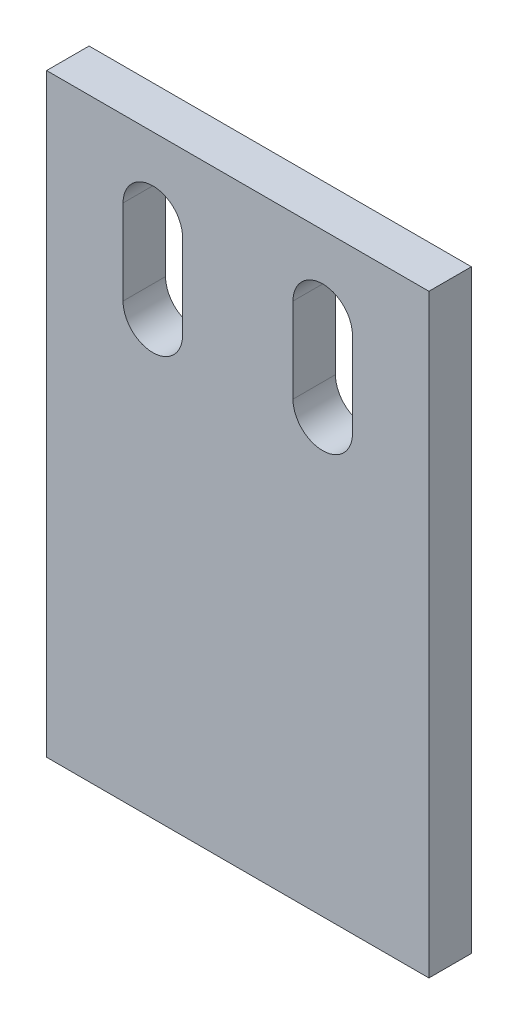
SolidWorks part; units mm, degrees
note: The reader was unsure of these and kept them because the rebuilt part matched: thickness of "Базовая кромка1", "Листовой металл1".
material "Простая углеродистая сталь"
ref_plane "Спереди" through (0, 0, 0) normal (0, 0, 1) x (1, 0, 0)
ref_plane "Сверху" through (0, 0, 0) normal (0, 1, 0) x (1, 0, 0)
ref_plane "Справа" through (0, 0, 0) normal (1, 0, 0) x (0, 0, -1)
sketch "Эскиз1" plane through (0, 0, 0) normal (0, 0, 1) x (1, 0, 0)
  line L0 (0, 0) -> (90, 0)
  line L1 (90, 0) -> (90, -140)
  line L5 (0, -140) -> (0, 0)
  line L6 (0, -140) -> (90, -140)
  line L7 (45, 0) -> (45, -41.8938) construction
  line L8 (25, -18) -> (25, -38) construction
  line L9 (32, -18) -> (32, -38)
  line L10 (18, -18) -> (18, -38)
  line L11 (65, -18) -> (65, -38) construction
  line L12 (58, -18) -> (58, -38)
  line L13 (72, -18) -> (72, -38)
  arc A0 (32, -18) -> (18, -18) centre (25, -18) ccw
  arc A1 (18, -38) -> (32, -38) centre (25, -38) ccw
  arc A2 (58, -18) -> (72, -18) centre (65, -18) cw
  arc A3 (72, -38) -> (58, -38) centre (65, -38) cw
  point P9 (25, -28)
  point P16 (65, -28)
  dimension "D3" = 20
  dimension "D1" = 14
  dimension "D2" = 90
  dimension "D4" = 140
  dimension "D5" = 28
  dimension "D6" = 40
base flange "Базовая кромка1" sketch "Эскиз1" thickness 10 reverse thickness direction no parameters "D1"=1
sketch "Сгиб-Линии1" [suppressed] plane through (0, 0, 0) normal (0, 1, 0) x (1, 0, 0)
sketch "Граничная рамка1" [suppressed] plane through (0, 0, 0) normal (0, 1, 0) x (1, 0, 0)
sheet metal parameters "Листовой металл1" thickness 10 parameters "D1"=1, "D7"=8
flat pattern "Развертка1" [suppressed]
sketch "Сгиб-Линии2" plane through (0, 0, 0) normal (0, 1, 0) x (1, 0, 0)
sketch3d "Граничная рамка2" [suppressed]
  line L0 (90, 0, 0) -> (90, -140, 0) construction
  line L1 (0, 0, 0) -> (0, -140, 0) construction
  line L2 (90, 0, 0) -> (0, 0, 0) construction
  line L3 (90, -140, 0) -> (0, -140, 0) construction
